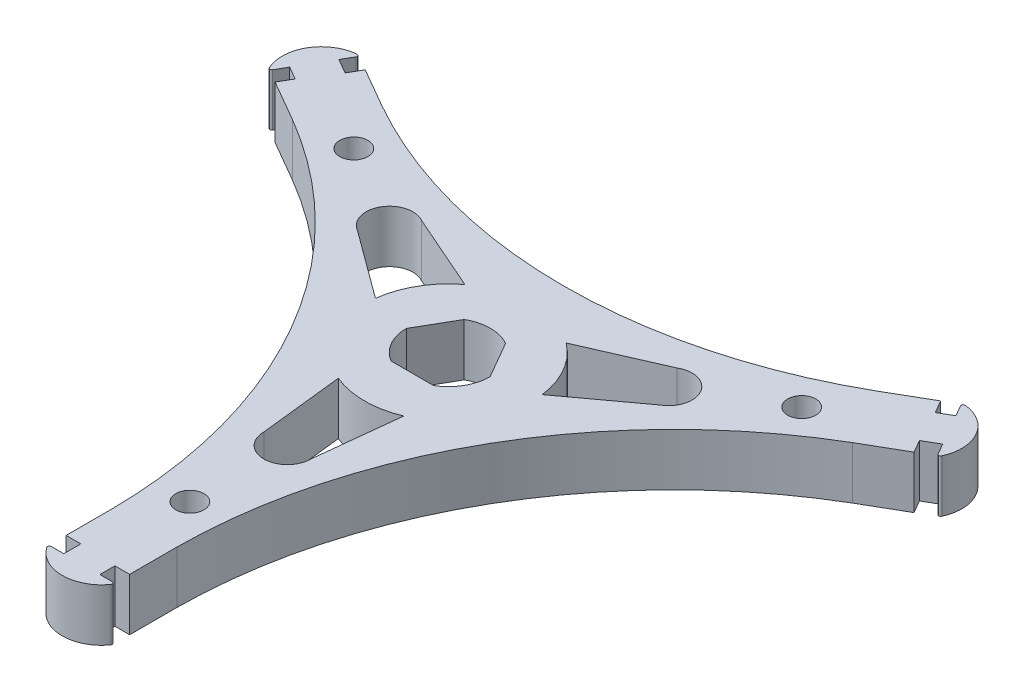
SolidWorks part; units mm, degrees
material "Plastique personnalisé"
ref_plane "前视基准面" through (0, 0, 0) normal (0, 0, 1) x (1, 0, 0)
ref_plane "上视基准面" through (0, 0, 0) normal (0, 1, 0) x (1, 0, 0)
ref_plane "右视基准面" through (0, 0, 0) normal (1, 0, 0) x (0, 0, -1)
sketch "Sketch1" plane through (0, 0, 0) normal (0, 1, 0) x (1, 0, 0)
  line L4 (4, 2.3094) -> (-8, -4.6188) construction
  line L5 (-4, 2.3094) -> (8, -4.6188) construction
  line L6 (0, 22.6075) -> (-18.985, 16.3546)
  line L7 (4, 2.3094) -> (-4.7631, -2.75) construction
  line L8 (-18.985, 16.3546) -> (-23.656, 8.2642)
  line L9 (-23.656, 8.2642) -> (-19.5787, -11.3038)
  line L10 (-4.6709, -24.6188) -> (-19.5787, -11.3038)
  line L11 (-4.6709, -24.6188) -> (4.6709, -24.6188)
  line L12 (4.6709, -24.6188) -> (19.5787, -11.3038)
  line L13 (23.656, 8.2642) -> (19.5787, -11.3038)
  line L14 (18.985, 16.3546) -> (23.656, 8.2642)
  line L15 (0, 22.6075) -> (18.985, 16.3546)
  line L16 (0, -4.6188) -> (0, 9.6216) construction
  line L17 (-2.6509, 5.046) -> (-5.6955, -0.2272) construction
  line L18 (-3.0445, -4.8188) -> (3.0445, -4.8188) construction
  line L19 (2.6509, 5.046) -> (5.6955, -0.2272) construction
  line L20 (-3.0132, 5.4185) -> (-6.1992, -0.0997) construction
  line L21 (-3.186, -5.3188) -> (3.186, -5.3188) construction
  line L22 (3.0132, 5.4185) -> (6.1992, -0.0997) construction
  line L23 (-3.159, 5.566) -> (-6.3998, -0.0472)
  line L24 (-3.2408, -5.5188) -> (3.2408, -5.5188)
  line L25 (3.159, 5.566) -> (6.3998, -0.0472)
  line L26 (-3.0132, 5.4185) -> (-6.1992, -0.0997) construction
  line L27 (-3.186, -5.3188) -> (3.186, -5.3188) construction
  line L28 (-14.2583, 10.5415) -> (-16.2583, 7.0774) construction
  line L29 (14.2583, 10.5415) -> (16.2583, 7.0774) construction
  line L30 (-2, -17.6188) -> (2, -17.6188) construction
  line L31 (0, 15.2376) -> (-14.2583, 10.5415) construction
  line L32 (0, 15.2376) -> (14.2583, 10.5415) construction
  line L33 (16.2583, 7.0774) -> (13.1962, -7.6188) construction
  line L34 (2, -17.6188) -> (13.1962, -7.6188) construction
  line L35 (-2, -17.6188) -> (-13.1962, -7.6188) construction
  line L36 (-16.2583, 7.0774) -> (-13.1962, -7.6188) construction
  line L37 (3.0132, 5.4185) -> (6.1992, -0.0997) construction
  arc A0 (3.159, 5.566) -> (-3.159, 5.566) centre (0, 0) ccw
  arc A1 (-6.3998, -0.0472) -> (-3.2408, -5.5188) centre (0, 0) ccw
  arc A2 (3.2408, -5.5188) -> (6.3998, -0.0472) centre (0, 0) ccw
  arc A3 (2.6509, 5.046) -> (-2.6509, 5.046) centre (0, 0) ccw construction
  arc A4 (-5.6955, -0.2272) -> (-3.0445, -4.8188) centre (0, 0) ccw construction
  arc A5 (3.0445, -4.8188) -> (5.6955, -0.2272) centre (0, 0) ccw construction
  arc A6 (3.0132, 5.4185) -> (-3.0132, 5.4185) centre (0, 0) ccw construction
  arc A7 (-6.1992, -0.0997) -> (-3.186, -5.3188) centre (0, 0) ccw construction
  arc A8 (3.186, -5.3188) -> (6.1992, -0.0997) centre (0, 0) ccw construction
  arc A9 (3.0132, 5.4185) -> (-3.0132, 5.4185) centre (0, 0) ccw construction
  arc A10 (-6.1992, -0.0997) -> (-3.186, -5.3188) centre (0, 0) ccw construction
  arc A11 (3.186, -5.3188) -> (6.1992, -0.0997) centre (0, 0) ccw construction
  point P0 (0, 9.2376)
  dimension "D4" = 0.5
  dimension "D1" = 7
  dimension "D2" = 0.2
  dimension "D3" = 16
extrude "Boss-Extrude1" add sketch "Sketch1" along normal blind 8
sketch "Sketch3" plane through (0, 8, 0) normal (0, 1, 0) x (1, 0, 0)
  line L0 (-10.0524, -5.8038) -> (-19.5787, -11.3038) construction
  line L1 (-18.985, 16.3546) -> (0, 25.03)
  line L2 (0, 25.03) -> (18.985, 16.3546)
  line L3 (23.656, 8.2642) -> (24.5343, -16.5322)
  line L4 (24.5343, -16.5322) -> (4.6709, -24.6188)
  line L5 (-23.656, 8.2642) -> (-26.3517, -12.5024)
  line L6 (-26.3517, -12.5024) -> (-4.6709, -24.6188)
  arc A0 (-23.656, 8.2642) -> (-4.6709, -24.6188) centre (-44.9855, -25.9724) cw
  arc A1 (18.985, 16.3546) -> (-18.985, 16.3546) centre (0, 51.9448) cw
  arc A2 (4.6709, -24.6188) -> (23.656, 8.2642) centre (44.9855, -25.9724) cw
  point P16 (0, 0)
  dimension "D1" = 11
  dimension "D2" = 3
extrude "Cut-Extrude1" cut sketch "Sketch3" against normal blind 10
sketch "Esquisse1" plane through (0, 0, 0) normal (0, -1, 0) x (1, 0, 0)
  line L0 (0, 0) -> (0, 46.5) construction
  line L1 (-5, 20.8452) -> (-5, 46.5)
  line L2 (5, 20.8452) -> (5, 46.5)
  line L3 (-5, 46.5) -> (5, 46.5)
  line L4 (-5, 20.8452) -> (5, 20.8452)
  line L6 (-5, 0) -> (-5, 46.5) construction
  line L7 (5, 0) -> (5, 46.5) construction
  circle A1 centre (0, 0) radius 46.5 construction
  circle A2 centre (0, 41.53) radius 1.8
  dimension "D2" = 93
  dimension "D5" = 3.6
  dimension "D3" = 5
  dimension "D4" = 5
extrude "Boss.-Extru.1" add sketch "Esquisse1" against normal blind 8 contours L1 L3 L2 L4
sketch "Esquisse2" plane through (0, 0, 0) normal (1, 0, 0) x (0, 0, -1)
  line L0 (0, 0) -> (0, 14.6767) construction
ref_axis "Axe1" through (0, 0, 0) along (0, 1, 0)
pattern_circular "Répétition circulaire3" count 3 every 120 about axis through (0, 0, 0) along (0, 1, 0) of "Boss.-Extru.1"
sketch "Esquisse3" plane through (0, 8, 0) normal (0, 1, 0) x (1, 0, 0)
  line L0 (0, 0) -> (-40.2702, 23.25) construction
  line L1 (-37.7702, 27.5801) -> (-42.7702, 18.9199) construction
  line L2 (40.2702, 23.25) -> (0, 0) construction
  line L3 (42.7702, 18.9199) -> (37.7702, 27.5801) construction
  line L4 (0, 0) -> (0, -46.5) construction
  line L5 (-5, -46.5) -> (5, -46.5) construction
  circle A1 centre (0, -39.5) radius 2.15
  circle A2 centre (34.208, 19.75) radius 2.15
  circle A4 centre (-34.208, 19.75) radius 2.15
  dimension "D1" = 7
  dimension "D2" = 4.3
  dimension "D5" = 4.3
  dimension "D6" = 4.3
  dimension "D3" = 7
  dimension "D4" = 7
extrude "Enlèv. mat.-Extru.1" cut sketch "Esquisse3" against normal blind 8
sketch "Esquisse5" plane through (0, 8, 0) normal (0, 1, 0) x (1, 0, 0)
  line L0 (0, -59) -> (0, -53) construction
  line L1 (-5, -46.5) -> (5, -46.5)
  line L2 (0, -56) -> (2.75, -56) construction
  line L3 (0, -56) -> (-2.75, -56) construction
  line L4 (-2.75, -56) -> (-4.6476, -56)
  line L5 (-5, -46.5) -> (-2.75, -56) construction
  line L6 (-5, -46.5) -> (-5, -53.4)
  line L7 (2.75, -56) -> (4.6476, -56)
  line L8 (5, -46.5) -> (2.75, -56) construction
  line L9 (-2.75, -53.4) -> (-2.75, -56)
  line L10 (5, -46.5) -> (5, -53.7)
  line L11 (2.75, -53.7) -> (5, -53.7)
  line L12 (2.75, -56) -> (2.75, -53.7)
  line L14 (-5, -53.4) -> (-2.75, -53.4)
  arc A0 (4.8922, -56.4737) -> (4.6476, -56) centre (4.6476, -56.3) ccw
  arc A1 (-4.8922, -56.4737) -> (4.8922, -56.4737) centre (0, -53) ccw
  arc A2 (-4.8922, -56.4737) -> (-4.6476, -56) centre (-4.6476, -56.3) cw
  dimension "D4" = 0.3
  dimension "D1" = 10
  dimension "D2" = 12.5
  dimension "D3" = 6
  dimension "D6" = 2.6
extrude "Boss.-Extru.4" add sketch "Esquisse5" against normal blind 8
pattern_circular "Répétition circulaire4" count 3 over 360 about axis through (0, 0, 0) along (0, 1, 0) of "Boss.-Extru.4"
sketch "Esquisse6" plane through (0, 8, 0) normal (0, 1, 0) x (1, 0, 0)
  line L0 (5.1661, -52.0473) -> (4.2422, -21.1924)
  line L1 (4.2422, -21.1924) -> (9.1345, -3.222)
  line L2 (9.1345, -3.222) -> (24.6334, 10.3797)
  line L3 (24.6334, 10.3797) -> (42.7702, 18.9199)
  arc A0 (5.1661, -52.0473) -> (42.7702, 18.9199) centre (81.3871, -46.9889) cw
  point P14 (0, 0)
extrude "Boss.-Extru.5" add sketch "Esquisse6" against normal blind 8 contours A0 region at (14.8021, 8, 7.122)
pattern_circular "Répétition circulaire5" count 3 every 120 about axis through (0, 0, 0) along (0, 1, 0) of "Boss.-Extru.5"
sketch "Esquisse12" plane through (0, 8, 0) normal (0, 1, 0) x (1, 0, 0)
  line L0 (-7.7354, 10.2395) -> (-19.5288, 15.4128)
  line L1 (-23.1122, 9.206) -> (-12.7354, 1.5793)
  line L2 (-5, -11.8188) -> (-3.5835, -24.6188)
  line L3 (3.5835, -24.6188) -> (5, -11.8188)
  line L5 (12.7354, 1.5793) -> (23.1122, 9.206)
  line L6 (19.5288, 15.4128) -> (7.7354, 10.2395)
  arc A2 (-3.5835, -24.6188) -> (3.5835, -24.6188) centre (0, -24.6188) ccw
  arc A3 (-5, -11.8188) -> (5, -11.8188) centre (0, 0) ccw
  arc A4 (-7.7354, 10.2395) -> (-12.7354, 1.5793) centre (0, 0) ccw
  arc A5 (-19.5288, 15.4128) -> (-23.1122, 9.206) centre (-21.3205, 12.3094) ccw
  arc A6 (12.7354, 1.5793) -> (7.7354, 10.2395) centre (0, 0) ccw
  arc A7 (23.1122, 9.206) -> (19.5288, 15.4128) centre (21.3205, 12.3094) ccw
  point P31 (0, 0)
  dimension "D3" = 3
extrude "Enlèv. mat.-Extru.4" cut sketch "Esquisse12" against normal blind 10
